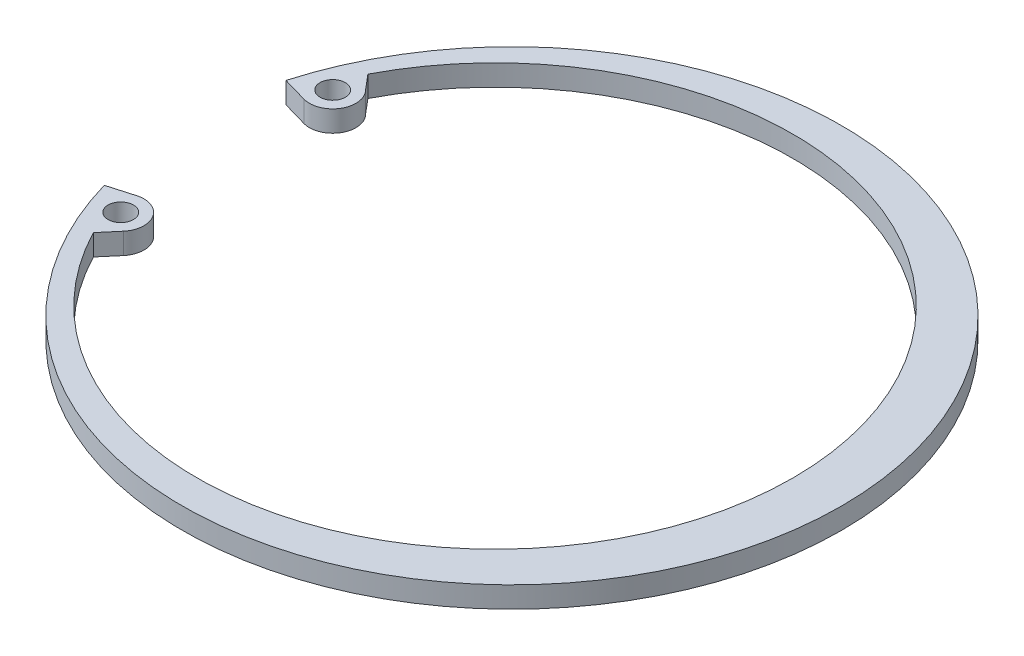
SolidWorks part; units mm, degrees
ref_plane "Front Plane" through (0, 0, 0) normal (0, 0, 1) x (1, 0, 0)
ref_plane "Top Plane" through (0, 0, 0) normal (0, 1, 0) x (1, 0, 0)
ref_plane "Right Plane" through (0, 0, 0) normal (1, 0, 0) x (0, 0, -1)
sketch "Sketch2" plane through (0, 0, 0) normal (0, 1, 0) x (1, 0, 0)
  line L0 (-37.4892, 10.7499) -> (0, 0) construction
  line L1 (0, 0) -> (-39, 0) construction
  line L2 (-19.5, 0) -> (-33.2857, 16.241) construction
  line L3 (-19.5, 0) -> (-33.2857, -16.241) construction
  line L4 (-37.4892, -10.7499) -> (0, 0) construction
  line L5 (-37.4892, 10.7499) -> (-34.508, 9.895)
  line L6 (-33.2857, 16.241) -> (-31.7882, 14.4656)
  line L7 (-33.2857, -16.241) -> (-31.6534, -14.3181)
  line L8 (-37.4892, -10.7499) -> (-34.508, -9.895)
  circle A0 centre (0, 0) radius 39 construction
  circle A1 centre (-2, 0) radius 35.25 construction
  circle A2 centre (-33.75, 12.5385) radius 1.5
  arc A3 (-34.508, 9.895) -> (-31.7882, 14.4656) centre (-33.75, 12.5385) ccw
  circle A4 centre (-33.75, -12.5385) radius 1.5
  arc A5 (-34.508, -9.895) -> (-31.6534, -14.3181) centre (-33.75, -12.5385) cw
  arc A6 (-37.4892, 10.7499) -> (-37.4892, -10.7499) centre (0, 0) cw
  arc A7 (-33.2857, 16.241) -> (-33.2857, -16.241) centre (-2, 0) cw
  dimension "D1" = 2
  dimension "D2" = 78
  dimension "D3" = 70.5
  dimension "D5" = 5.5
  dimension "D6" = 3
  dimension "D7" = 33.75
  dimension "D4" = 16
base flange "Base-Flange1" sketch "Sketch2" thickness 2.5 reverse thickness direction no parameters "D1"=1
sketch "Bend-Lines1" [suppressed] plane through (0, 0, 0) normal (0, 1, 0) x (1, 0, 0)
sketch "Bounding-Box1" [suppressed] plane through (0, 0, 0) normal (0, 1, 0) x (1, 0, 0)
sheet metal parameters "Sheet-Metal1" thickness 2.5 parameters "D1"=1
flat pattern "Flat-Pattern1" [suppressed]
sketch "Bend-Lines2" plane through (0, 0, 0) normal (0, 1, 0) x (1, 0, 0)
sketch3d "Bounding-Box2" [suppressed]
  line L0 (37.4892, -39, 0) -> (37.4892, 39, 0) construction
  line L1 (-39, -39, 0) -> (-39, 39, 0) construction
  line L2 (37.4892, -39, 0) -> (-39, -39, 0) construction
  line L3 (37.4892, 39, 0) -> (-39, 39, 0) construction
